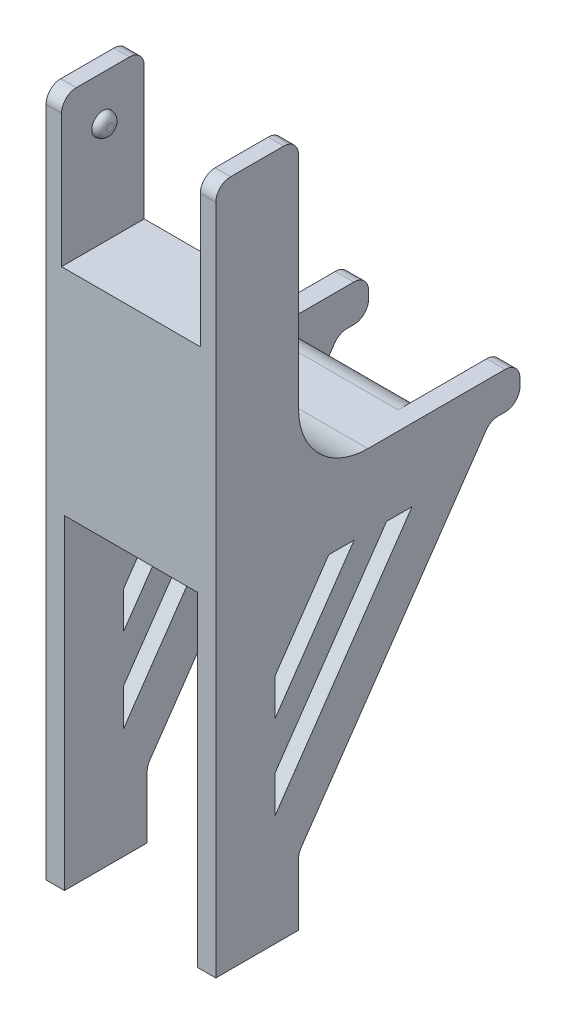
SolidWorks part; units mm, degrees
ref_plane "Front Plane" through (0, 0, 0) normal (0, 0, 1) x (1, 0, 0)
ref_plane "Top Plane" through (0, 0, 0) normal (0, 1, 0) x (1, 0, 0)
ref_plane "Right Plane" through (0, 0, 0) normal (1, 0, 0) x (0, 0, -1)
sketch "Szkic1" plane through (0, 0, 0) normal (1, 0, 0) x (0, 0, -1)
  line L2 (0, 0) -> (-10.3, 0)
  line L5 (-15, 4.7) -> (-15, 20.6)
  line L6 (-15, 20.6) -> (-20.6, 20.6)
  line L7 (-20.6, 20.6) -> (-20.6, -21.4)
  line L8 (0, 0) -> (0, -2.5)
  line L9 (0, -2.5) -> (-2, -2.5)
  line L10 (-2, -2.5) -> (-15, -21.4)
  line L11 (-15, -21.4) -> (-15, -25.9)
  line L12 (-15, -25.9) -> (-20.6, -25.9)
  line L13 (-20.6, -25.9) -> (-20.6, -21.4)
  arc A0 (-15, 4.7) -> (-10.3, 0) centre (-10.3, 4.7) ccw
  point P15 (-10.3, 4.7)
  dimension "D5" = 2.5
  dimension "D7" = 4.7
  dimension "D1" = 42
  dimension "D2" = 20.6
  dimension "D3" = 15.9
  dimension "D4" = 5.6
  dimension "D6" = 2
  dimension "D8" = 18.9
  dimension "D9" = 4.5
extrude "Dodanie-wyciągnięcie1" add sketch "Szkic1" along normal blind 11.5
ref_plane "Płaszczyzna dolna" through (0, 0, 20.6) normal (0, 0, 1) x (1, 0, 0)
sketch "Szkic2" plane through (0, 0, 20.6) normal (0, 0, 1) x (1, 0, 0)
  line L0 (5.75, 20.6) -> (5.75, -25.9) construction
  line L1 (11.5, 20.6) -> (0, 20.6) construction
  line L2 (11.5, -25.9) -> (0, -25.9) construction
  line L4 (10.45, 10.6) -> (1.05, 10.6)
  line L5 (10.45, 10.6) -> (10.45, 20.6)
  line L6 (10.45, 20.6) -> (1.05, 20.6)
  line L7 (1.05, 10.6) -> (1.05, 20.6)
  line L8 (10.45, 10.6) -> (1.05, 20.6) construction
  line L9 (10.45, 20.6) -> (1.05, 10.6) construction
  line L10 (10.25, -3.9) -> (1.25, -3.9)
  line L11 (10.25, -3.9) -> (10.25, -25.9)
  line L12 (10.25, -25.9) -> (1.25, -25.9)
  line L13 (1.25, -3.9) -> (1.25, -25.9)
  line L14 (10.25, -3.9) -> (1.25, -25.9) construction
  line L15 (10.25, -25.9) -> (1.25, -3.9) construction
  point P6 (5.75, 15.6)
  point P11 (5.75, -14.9)
  dimension "D1" = 9.4
  dimension "D2" = 10
  dimension "D3" = 9
  dimension "D4" = 22
extrude "Wytnij-wyciągnięcie1" cut sketch "Szkic2" against normal through all
ref_plane "Płaszczyzna boczna" through (11.5, 0, 0) normal (1, 0, 0) x (0, 0, -1)
sketch "Szkic3" plane through (11.5, 0, 0) normal (1, 0, 0) x (0, 0, -1)
  line L0 (-16.6, -12.7056) -> (-16.6, -10.1985)
  line L1 (-16.6, -10.1985) -> (-12.9555, -4.9)
  line L2 (-12.9555, -4.9) -> (-11.2311, -4.9)
  line L3 (-11.2311, -4.9) -> (-16.6, -12.7056)
  line L4 (-16.6, -15.8972) -> (-16.6, -18.4043)
  line L5 (-16.6, -18.4043) -> (-7.3113, -4.9)
  line L6 (-7.3113, -4.9) -> (-9.0358, -4.9)
  line L7 (-9.0358, -4.9) -> (-16.6, -15.8972)
  line L8 (-15, -21.4) -> (-2, -2.5) construction
  line L10 (-20.6, 6.325) -> (-20.6, -6.325) construction
  line L11 (-20.6, -25.9) -> (-15, -25.9) construction
  dimension "D1" = 4
  dimension "D2" = 21
extrude "Wytnij-wyciągnięcie2" cut sketch "Szkic3" against normal through all both and the other way through all
ref_plane "Płaszczyzna3" through (0, 0, 0) normal (0, 1, 0) x (1, 0, 0)
sketch "Szkic4" plane through (0, 0, 0) normal (0, 1, 0) x (1, 0, 0)
  line L0 (5.75, -5) -> (5.75, 0) construction
  line L2 (11.5, 0) -> (0, 0) construction
  line L4 (1.25, -5) -> (10.25, -5)
  line L5 (1.25, -5) -> (1.25, 0)
  line L6 (1.25, 0) -> (10.25, 0)
  line L7 (10.25, -5) -> (10.25, 0)
  line L8 (1.25, -5) -> (10.25, 0) construction
  line L9 (1.25, 0) -> (10.25, -5) construction
  point P6 (5.75, -2.5)
  dimension "D1" = 9
  dimension "D2" = 5
extrude "Wytnij-wyciągnięcie3" cut sketch "Szkic4" against normal blind 10
fillet "Zaokrąglenie1" radius 2 2 edges at (5.75, -3.9, 5) (5.75, 0, 5)
fillet "Zaokrąglenie2" radius 1 12 edges at (0.625, 0, 0) (0.625, -2.5, 0) (10.875, -2.5, 0) (10.875, 0, 0) (10.975, 20.6, 20.6) (10.975, 20.6, 15) (0.525, 20.6, 20.6) (0.525, 20.6, 15) (0.625, -2.5, 2) (10.875, -2.5, 2) (0.625, -21.4, 15) (10.875, -21.4, 15)
ref_plane "Płaszczyzna4" through (10.45, 0, 0) normal (-1, 0, 0) x (0, 0, 1)
sketch "Szkic5" plane through (10.45, 0, 0) normal (-1, 0, 0) x (0, 0, 1)
  line L3 (17.8, 20.6) -> (17.8, 10.6) construction
  line L4 (16, 20.6) -> (19.6, 20.6) construction
  line L5 (15, 10.6) -> (20.6, 10.6) construction
  circle A0 centre (17.8, 17.6) radius 0.75
  dimension "D1" = 1.5
  dimension "D2" = 3
extrude "Dodanie-wyciągnięcie2" add sketch "Szkic5" along normal blind 0.5
fillet "Zaokrąglenie3" radius 0.5 1 edges at (9.95, 16.85, 17.8)
ref_plane "Płaszczyzna5" through (5.75, 0, 0) normal (1, 0, 0) x (0, 0, -1)
mirror "Lustro2" about plane through (5.75, 0, 0) normal (1, 0, 0) of bodies 113 115
ref_plane "Płaszczyzna6" through (0, -25.9, 0) normal (0, -1, 0) x (-1, 0, 0)
sketch "Szkic7" plane through (0, -25.9, 0) normal (0, -1, 0) x (-1, 0, 0)
  line L0 (-10.45, -15) -> (-10.45, -20.6) construction
  line L1 (-11.5, -15) -> (-10.25, -15) construction
  line L2 (-6.325, -20.6) -> (6.325, -20.6) construction
  line L3 (-10.45, -17.8) -> (-1.25, -17.8)
  line L4 (-1.25, -15) -> (-1.25, -20.6) construction
  line L5 (-10.45, -3.08) -> (-10.45, 3.08) construction
  point P6 (-10.45, -17.8)
  point P14 (-5.85, -17.8)
ref_point "Punkt1"
